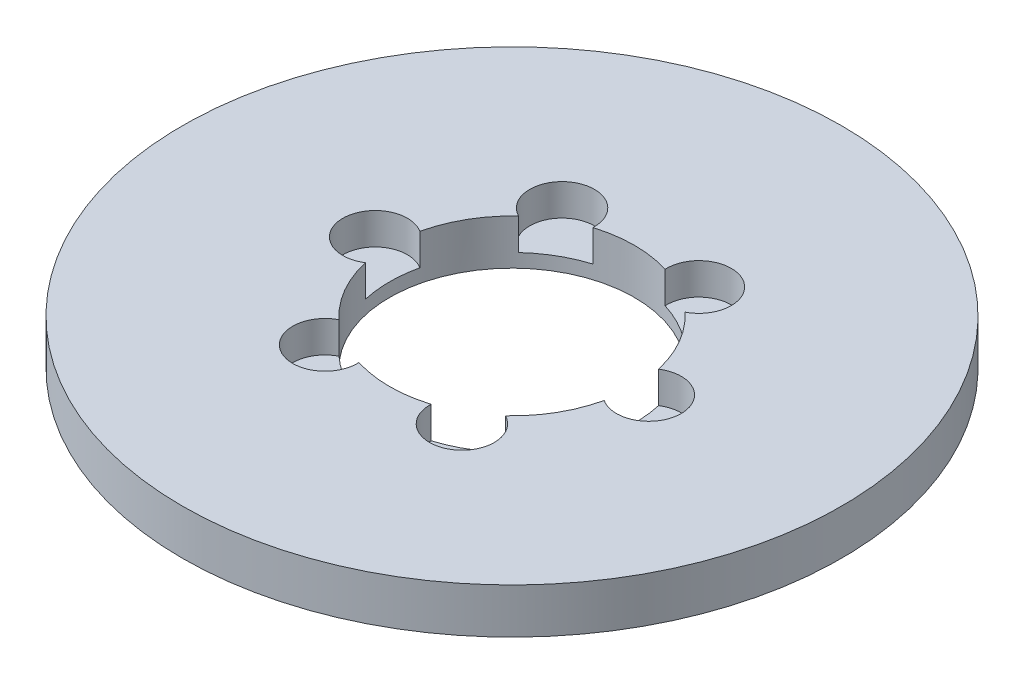
SolidWorks part; units mm, degrees
ref_plane "Front Plane" through (0, 0, 0) normal (0, 0, 1) x (1, 0, 0)
ref_plane "Top Plane" through (0, 0, 0) normal (0, 1, 0) x (1, 0, 0)
ref_plane "Right Plane" through (0, 0, 0) normal (1, 0, 0) x (0, 0, -1)
sketch "Sketch1" plane through (0, 0, 0) normal (0, 1, 0) x (1, 0, 0)
  circle A0 centre (0, 0) radius 87.5
  dimension "FLANGE_OD" = 175
extrude "Boss-Extrude1" add sketch "Sketch1" along normal blind 12
sketch "Sketch2" plane through (0, 0, 0) normal (0, 1, 0) x (1, 0, 0)
  circle A0 centre (0, 0) radius 32.5
  dimension "BORE_D" = 65
extrude "Cut-Extrude1" cut sketch "Sketch2" along normal through all
sketch "Sketch3" plane through (0, 12, 0) normal (0, 1, 0) x (1, 0, 0)
  circle A0 centre (0, 0) radius 36.3336 construction
  circle A1 centre (-36.3336, 0) radius 8.5856
  dimension "BOLT_D" = 17.1713
  dimension "BOLT_PCD" = 72.6672
extrude "Cut-Extrude2" cut sketch "Sketch3" against normal blind 8.3939
pattern_circular "CirPattern1" count 6 over 360 about axis through (0, 0, 0) along (0, 1, 0) of "Cut-Extrude2"
